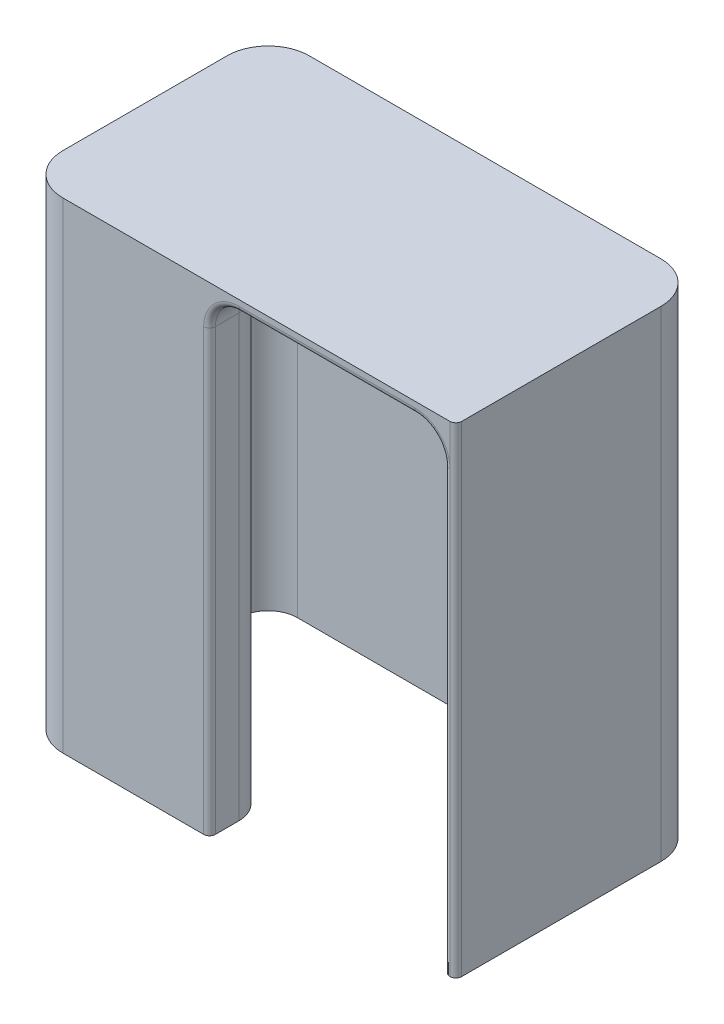
SolidWorks part; units mm, degrees
ref_plane "Front Plane" through (0, 0, 0) normal (0, 0, 1) x (1, 0, 0)
ref_plane "Top Plane" through (0, 0, 0) normal (0, 1, 0) x (1, 0, 0)
ref_plane "Right Plane" through (0, 0, 0) normal (1, 0, 0) x (0, 0, -1)
sketch "Sketch1" plane through (0, 0, 0) normal (0, 1, 0) x (1, 0, 0)
  line L0 (0, 0) -> (74, 0)
  line L1 (74, 0) -> (74, -42)
  line L2 (74, -42) -> (72, -42)
  line L3 (72, -42) -> (72, -2)
  line L4 (72, -2) -> (2, -2)
  line L5 (2, -2) -> (2, -32)
  line L6 (2, -32) -> (32, -32)
  line L7 (32, -32) -> (32, -42)
  line L8 (32, -42) -> (0, -42)
  line L9 (0, -42) -> (0, 0)
  dimension "D1" = 40
  dimension "D2" = 2
  dimension "D3" = 2
  dimension "D4" = 2
  dimension "D5" = 30
  dimension "D6" = 30
  dimension "D7" = 10
extrude "Boss-Extrude1" add sketch "Sketch1" along normal blind 80
sketch "Sketch2" plane through (0, 80, 0) normal (0, 1, 0) x (1, 0, 0)
  line L1 (0, 0) -> (74, 0)
  line L2 (0, 0) -> (0, -42)
  line L3 (0, -42) -> (74, -42)
  line L4 (74, 0) -> (74, -42)
extrude "Boss-Extrude2" add sketch "Sketch2" along normal blind 2
fillet "Fillet1" radius 5 4 edges at (32, 40, 32) (2, 40, 32) (72, 40, 2) (2, 40, 2)
fillet "Fillet2" radius 7 3 edges at (0, 41, 0) (0, 41, 42) (74, 41, 0)
fillet "Fillet3" radius 5 9 edges at (32, 80, 39.5) (30.5355, 80, 33.4645) (17, 80, 32) (3.4645, 80, 30.5355) (2, 80, 17) (3.4645, 80, 3.4645) (72, 80, 24.5) (70.5355, 80, 3.4645) (37, 80, 2)
fillet "Fillet5" radius 1 6 edges at (72, 37.5, 42) (70.5355, 78.5355, 42) (52, 80, 42) (33.4645, 78.5355, 42) (74, 41, 42) (32, 37.5, 42)
sketch "Sketch3" plane through (0, 0, 32) normal (0, 0, -1) x (-1, 0, 0)
  line L1 (-12, 67.5) -> (-22, 67.5) construction
  line L2 (-12, 67.5) -> (-12, 72.5) construction
  line L3 (-12, 72.5) -> (-22, 72.5) construction
  line L4 (-22, 67.5) -> (-22, 72.5) construction
  line L5 (-12, 67.5) -> (-22, 72.5) construction
  line L6 (-12, 72.5) -> (-22, 67.5) construction
  line L7 (-12, 55.5) -> (-22, 55.5) construction
  line L8 (-12, 55.5) -> (-12, 60.5) construction
  line L9 (-12, 60.5) -> (-22, 60.5) construction
  line L10 (-22, 55.5) -> (-22, 60.5) construction
  line L11 (-12, 55.5) -> (-22, 60.5) construction
  line L12 (-12, 60.5) -> (-22, 55.5) construction
  line L13 (-12, 43.5) -> (-22, 43.5) construction
  line L14 (-12, 43.5) -> (-12, 48.5) construction
  line L15 (-12, 48.5) -> (-22, 48.5) construction
  line L16 (-22, 43.5) -> (-22, 48.5) construction
  line L17 (-12, 43.5) -> (-22, 48.5) construction
  line L18 (-12, 48.5) -> (-22, 43.5) construction
  line L19 (-12, 31.5) -> (-22, 31.5) construction
  line L20 (-12, 31.5) -> (-12, 36.5) construction
  line L21 (-12, 36.5) -> (-22, 36.5) construction
  line L22 (-22, 31.5) -> (-22, 36.5) construction
  line L23 (-12, 31.5) -> (-22, 36.5) construction
  line L24 (-12, 36.5) -> (-22, 31.5) construction
  line L25 (-12, 19.5) -> (-22, 19.5) construction
  line L26 (-12, 19.5) -> (-12, 24.5) construction
  line L27 (-12, 24.5) -> (-22, 24.5) construction
  line L28 (-22, 19.5) -> (-22, 24.5) construction
  line L29 (-12, 19.5) -> (-22, 24.5) construction
  line L30 (-12, 24.5) -> (-22, 19.5) construction
  line L31 (-12, 7.5) -> (-22, 7.5) construction
  line L32 (-12, 7.5) -> (-12, 12.5) construction
  line L33 (-12, 12.5) -> (-22, 12.5) construction
  line L34 (-22, 7.5) -> (-22, 12.5) construction
  line L35 (-12, 7.5) -> (-22, 12.5) construction
  line L36 (-12, 12.5) -> (-22, 7.5) construction
  line L38 (-17, 70) -> (-17, 80) construction
  line L39 (-17, 10) -> (-17, 0) construction
  line L40 (-27, 80) -> (-7, 80) construction
  line L42 (-27, 0) -> (-7, 0) construction
  circle A0 centre (-12, 72.5) radius 1
  circle A1 centre (-12, 67.5) radius 1
  circle A2 centre (-12, 60.5) radius 1
  circle A3 centre (-12, 48.5) radius 1
  circle A4 centre (-17, 43.5) radius 1
  circle A5 centre (-17, 48.5) radius 1
  circle A6 centre (-22, 48.5) radius 1
  circle A7 centre (-12, 36.5) radius 1
  circle A8 centre (-17, 31.5) radius 1
  circle A9 centre (-22, 36.5) radius 1
  circle A10 centre (-12, 24.5) radius 1
  circle A11 centre (-17, 24.5) radius 1
  circle A12 centre (-22, 24.5) radius 1
  circle A13 centre (-22, 12.5) radius 1
  circle A14 centre (-17, 12.5) radius 1
  circle A15 centre (-12, 7.5) radius 1
  point P0 (-17, 70)
  point P6 (-17, 58)
  point P11 (-17, 46)
  point P16 (-17, 34)
  point P21 (-17, 22)
  point P26 (-17, 10)
  dimension "D5" = 2
  dimension "D1" = 5
  dimension "D2" = 10
  dimension "D4" = 12
  dimension "D3" = 6
extrude "Boss-Extrude4" add sketch "Sketch3" along normal blind 0.5
chamfer "Chamfer1" distance 0.5 angle 30 16 edges at (23, 12.5, 32) (23, 24.5, 32) (23, 36.5, 32) (23, 48.5, 32) (18, 48.5, 32) (18, 43.5, 32) (18, 31.5, 32) (18, 24.5, 32) (18, 12.5, 32) (13, 7.5, 32) (13, 24.5, 32) (13, 36.5, 32) (13, 48.5, 32) (13, 60.5, 32) (13, 67.5, 32) (13, 72.5, 32) first distance on face at (21, 12.5, 31.5) first distance on face at (21, 24.5, 31.5) first distance on face at (21, 36.5, 31.5) first distance on face at (21, 48.5, 31.5) first distance on face at (16, 48.5, 31.5) first distance on face at (16, 43.5, 31.5) first distance on face at (16, 31.5, 31.5) first distance on face at (16, 24.5, 31.5) first distance on face at (16, 12.5, 31.5) first distance on face at (11, 7.5, 31.5) first distance on face at (11, 24.5, 31.5) first distance on face at (11, 36.5, 31.5) first distance on face at (11, 48.5, 31.5) first distance on face at (11, 60.5, 31.5) first distance on face at (11, 67.5, 31.5) first distance on face at (11, 72.5, 31.5)
